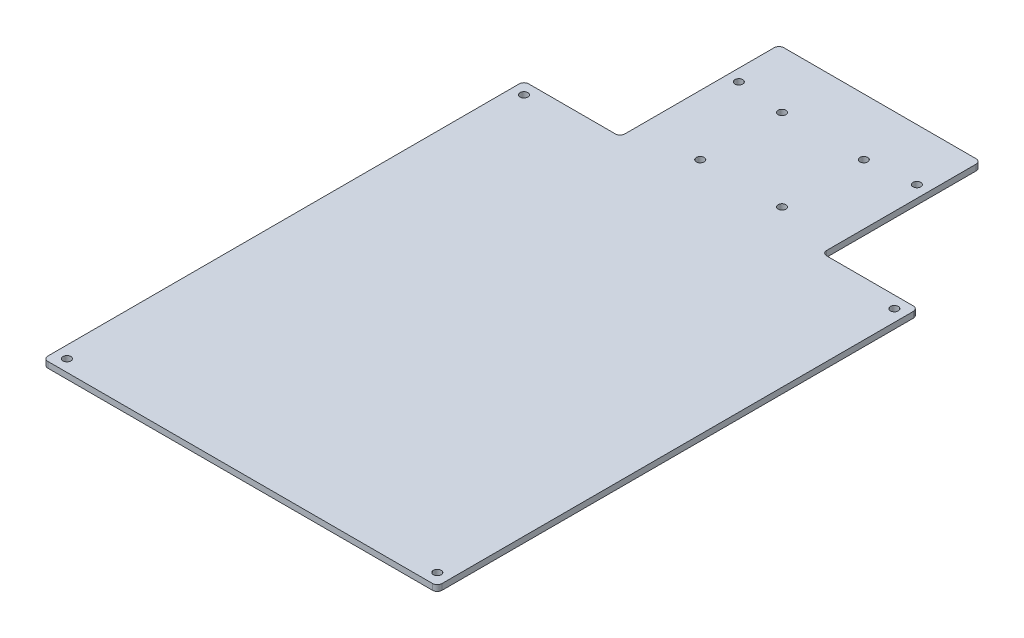
SolidWorks part; units mm, degrees
ref_plane "Front Plane" through (0, 0, 0) normal (0, 0, 1) x (1, 0, 0)
ref_plane "Top Plane" through (0, 0, 0) normal (0, 1, 0) x (1, 0, 0)
ref_plane "Right Plane" through (0, 0, 0) normal (1, 0, 0) x (0, 0, -1)
sketch "Sketch1" plane through (0, 0, 0) normal (0, 1, 0) x (1, 0, 0)
  line L0 (-12.7, -12.7) -> (198.12, -12.7)
  line L1 (0, 0) -> (185.42, 0)
  line L2 (0, 0) -> (0, 231.775)
  line L3 (0, 231.775) -> (185.42, 231.775)
  line L4 (185.42, 0) -> (185.42, 231.775)
  line L5 (198.12, -12.7) -> (198.12, 244.475)
  line L6 (-12.7, 244.475) -> (198.12, 244.475)
  line L7 (-12.7, -12.7) -> (-12.7, 244.475)
  dimension "D1" = 185.42
  dimension "D2" = 231.775
  dimension "D3" = 12.7
extrude "Boss-Extrude1" add sketch "Sketch1" along normal blind 3.175 contours L1 L4 L3 L2 | L7 L0 L5 L6 L4 L1 L2 L3 region at (-9.3746, 0, -115.8875) region at (92.71, 0, -115.8875)
sketch "Sketch2" plane through (0, 3.175, 0) normal (0, 1, 0) x (1, 0, 0)
  line L0 (23.1775, 231.775) -> (23.1775, 0)
  line L1 (46.355, 231.775) -> (46.355, 0)
  line L2 (69.5325, 231.775) -> (69.5325, 0)
  line L3 (92.71, 231.775) -> (92.71, 0)
  line L4 (0, 0) -> (185.42, 0)
  line L5 (185.42, 0) -> (185.42, 231.775)
  line L6 (185.42, 231.775) -> (0, 231.775)
  line L7 (0, 231.775) -> (0, 0)
  line L8 (0, 0) -> (185.42, 0)
  line L9 (185.42, 0) -> (185.42, 231.775)
  line L10 (185.42, 231.775) -> (0, 231.775)
  line L11 (0, 231.775) -> (0, 0)
  line L12 (-12.7, -12.7) -> (198.12, -12.7)
  line L13 (198.12, -12.7) -> (198.12, 244.475)
  line L14 (198.12, 244.475) -> (-12.7, 244.475)
  line L15 (-12.7, 244.475) -> (-12.7, -12.7)
  line L16 (-12.7, -12.7) -> (198.12, -12.7)
  line L17 (198.12, -12.7) -> (198.12, 244.475)
  line L18 (198.12, 244.475) -> (-12.7, 244.475)
  line L19 (-12.7, 244.475) -> (-12.7, -12.7)
  line L20 (115.8875, 231.775) -> (115.8875, 0)
  line L21 (139.065, 231.775) -> (139.065, 0)
  line L22 (162.2425, 231.775) -> (162.2425, 0)
  line L23 (0, 28.9719) -> (185.42, 28.9719)
  line L24 (0, 57.9437) -> (185.42, 57.9437)
  line L25 (0, 86.9156) -> (185.42, 86.9156)
  line L26 (0, 115.8875) -> (185.42, 115.8875)
  line L27 (0, 144.8594) -> (185.42, 144.8594)
  line L28 (0, 173.8312) -> (185.42, 173.8312)
  line L29 (0, 202.8031) -> (185.42, 202.8031)
  dimension "D1" = 0
  dimension "D2" = 0
  dimension "D3" = 8
  dimension "D4" = 8
sketch "Sketch3" plane through (0, 3.175, 0) normal (0, 1, 0) x (1, 0, 0)
  line L0 (185.42, 231.775) -> (0, 231.775) construction
  line L1 (92.71, 231.775) -> (92.71, 322.435)
  line L2 (0, 231.775) -> (-12.7, 244.475) construction
  line L3 (38.735, 231.775) -> (146.685, 231.775)
  line L4 (38.735, 231.775) -> (38.735, 307.975)
  line L5 (38.735, 307.975) -> (146.685, 307.975)
  line L6 (146.685, 231.775) -> (146.685, 307.975)
  line L7 (185.42, 231.775) -> (198.12, 244.475) construction
  line L8 (-12.7, -12.7) -> (0, 0) construction
  line L9 (198.12, -12.7) -> (185.42, 0) construction
  line L11 (146.685, 307.975) -> (140.335, 307.975)
  line L12 (146.685, 307.975) -> (146.685, 301.625)
  line L13 (146.685, 301.625) -> (140.335, 301.625)
  line L14 (140.335, 307.975) -> (140.335, 301.625)
  line L15 (38.735, 307.975) -> (45.085, 307.975)
  line L16 (38.735, 307.975) -> (38.735, 301.625)
  line L17 (38.735, 301.625) -> (45.085, 301.625)
  line L18 (45.085, 307.975) -> (45.085, 301.625)
  line L19 (38.735, 307.975) -> (146.685, 307.975)
  line L20 (38.735, 307.975) -> (38.735, 329.4634)
  line L21 (38.735, 329.4634) -> (146.685, 329.4634)
  line L22 (146.685, 307.975) -> (146.685, 329.4634)
  circle A0 centre (92.71, 277.105) radius 45.33
  circle A1 centre (-6.35, 238.125) radius 2.0955
  circle A2 centre (191.77, 238.125) radius 2.0955
  circle A3 centre (191.77, -6.35) radius 2.0955
  circle A4 centre (-6.35, -6.35) radius 2.0955
  circle A5 centre (140.335, 301.625) radius 2.0955
  circle A6 centre (45.085, 301.625) radius 2.0955
  point P0 (92.71, 231.775)
  line M12 (198.12, 244.475) -> (-12.7, 244.475)
  dimension "D9" = 4.191
  dimension "D1" = 90.66
  dimension "D2" = 76.2
  dimension "D3" = 107.95
  dimension "D4" = 6.35
  dimension "D5" = 6.35
  dimension "D6" = 6.35
  dimension "D7" = 6.35
  dimension "D8" = 97.6884
extrude "Cut-Extrude1" cut sketch "Sketch3" against normal blind 3.175 contours A2 | A3 | A4 | A1 region at (-6.35, 3.175, -238.125) region at (191.77, 3.175, -238.125) region at (191.77, 3.175, 6.35) region at (-6.35, 3.175, 6.35)
extrude "Boss-Extrude2" add sketch "Sketch3<3>" against normal blind 3.175 contours A5 L14 L5 A0 L6 L13 M12 | A5 L13 L6 L5 L14 | A6 L17 L4 A0 L5 L18 M12 | A6 L18 L5 L4 L17 | A0 L1 M12 | L1 A0 M12 | A0 L19 L5 L22 L21 L20 | L5 A0 L1 | L1 A0 L19 region at (71.8982, 3.175, -276.4155) region at (113.5218, 3.175, -276.4155) region at (45.8548, 3.175, -273.696) region at (139.5652, 3.175, -273.696) region at (79.9468, 3.175, -313.8462) region at (105.4732, 3.175, -313.8462) region at (52.3004, 3.175, -309.0757) region at (41.6962, 3.175, -305.0138) region at (143.7238, 3.175, -305.0138)
sketch "Sketch3<3>" plane through (0, 3.175, 0) normal (0, 1, 0) x (1, 0, 0) same geometry as "Sketch3"
fillet "Fillet1" radius 2.54 8 edges at (38.735, 1.5875, -244.475) (146.685, 1.5875, -244.475) (-12.7, 1.5875, 12.7) (-12.7, 1.5875, -244.475) (198.12, 1.5875, -244.475) (198.12, 1.5875, 12.7) (38.735, 1.5875, -329.4634) (146.685, 1.5875, -329.4634)
sketch "Sketch4" plane through (0, 3.175, 0) normal (0, 1, 0) x (1, 0, 0)
  line L1 (70.8341, 255.2291) -> (114.5859, 255.2291)
  line L2 (70.8341, 255.2291) -> (70.8341, 298.9809)
  line L3 (70.8341, 298.9809) -> (114.5859, 298.9809)
  line L4 (114.5859, 255.2291) -> (114.5859, 298.9809)
  line L5 (70.8341, 255.2291) -> (114.5859, 298.9809) construction
  line L6 (70.8341, 298.9809) -> (114.5859, 255.2291) construction
  arc A0 (59.5158, 307.975) -> (125.9042, 307.975) centre (92.71, 277.105) ccw construction
  arc A1 (59.5158, 307.975) -> (125.9042, 307.975) centre (92.71, 277.105) ccw
  circle A2 centre (70.8341, 298.9809) radius 2.0955
  circle A3 centre (114.5859, 298.9809) radius 2.0955
  circle A4 centre (114.5859, 255.2291) radius 2.0955
  circle A5 centre (70.8341, 255.2291) radius 2.0955
  point P5 (92.71, 277.105)
  dimension "D2" = 4.191
  dimension "D1" = 30.9372
extrude "Cut-Extrude2" cut sketch "Sketch4" against normal up to surface (3.175 mm away) contours A2 | A3 | A4 | A5 up to face at (-6.35, 0, -236.0295)
